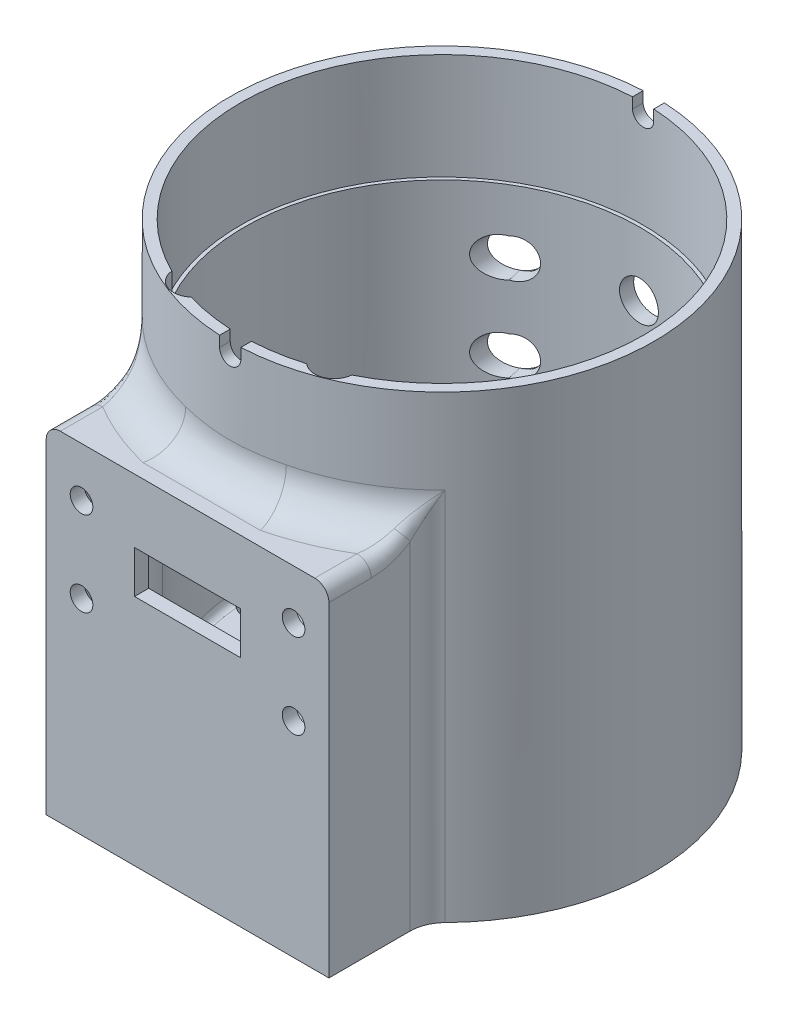
SolidWorks part; units mm, degrees
note: '?' marks a value the reader was unsure of.
material "自定义塑料"
ref_plane "前视基准面" through (0, 0, 0) normal (0, 0, 1) x (1, 0, 0)
ref_plane "上视基准面" through (0, 0, 0) normal (0, 1, 0) x (1, 0, 0)
ref_plane "右视基准面" through (0, 0, 0) normal (1, 0, 0) x (0, 0, -1)
sketch "草图1" plane through (0, 0, 0) normal (0, 1, 0) x (1, 0, 0)
  line L5 (15.5, 15.5) -> (-15.5, 15.5)
  line L6 (15.5, 15.5) -> (15.5, -15.5)
  line L7 (-3.3588, 3.3588) -> (3.3588, -3.3588) construction
  line L8 (15.5, -15.5) -> (-15.5, -15.5)
  line L9 (-15.5, 15.5) -> (-15.5, -15.5)
  line L10 (15.5, 15.5) -> (-15.5, -15.5) construction
  line L11 (15.5, -15.5) -> (-15.5, 15.5) construction
  circle A1 centre (0, 0) radius 30
  circle A6 centre (0, 0) radius 4.75
  circle A7 centre (-15.5, 15.5) radius 1.6
  circle A8 centre (15.5, 15.5) radius 1.6
  circle A9 centre (15.5, -15.5) radius 1.6
  circle A10 centre (-15.5, -15.5) radius 1.6
  point P17 (0, 0)
  point P20 (0, 0)
  dimension "D1" = 4
  dimension "D3" = 60
extrude "凸台-拉伸1" add sketch "草图1" along normal blind 5
sketch "草图2" plane through (0, 5, 0) normal (0, 1, 0) x (1, 0, 0)
  circle A0 centre (0, 0) radius 11.1
extrude "切除-拉伸1" cut sketch "草图2" against normal blind 2.2
sketch "草图4" plane through (0, 5, 0) normal (0, 1, 0) x (1, 0, 0)
  circle A0 centre (0, 0) radius 30
  circle A1 centre (0, 0) radius 28
extrude "凸台-拉伸2" add sketch "草图4" along normal blind 60
fillet "圆角1" radius 1 1 edges at (0, 5, 28)
ref_plane "基准面1" through (0, 0, 34) normal (0, 0, 1) x (1, 0, 0)
sketch "草图6" plane through (0, 0, 34) normal (0, 0, 1) x (1, 0, 0)
  line L0 (0, 0) -> (0, 7.1062)
  line L1 (-30, 0) -> (30, 0) construction
  line L2 (-18, 41) -> (-18, 5)
  line L3 (-15, 26) -> (15, 26)
  line L4 (-15, 26) -> (-15, 14)
  line L5 (-15, 14) -> (15, 14)
  line L6 (15, 26) -> (15, 14)
  line L7 (-15, 26) -> (15, 14) construction
  line L8 (-15, 14) -> (15, 26) construction
  line L13 (-10.8, 26) -> (10.8, 14) construction
  line L14 (-10.8, 14) -> (10.8, 26) construction
  line L19 (18, 41) -> (18, 5)
  line L20 (10, 26) -> (-16.6667, 10) construction
  line L23 (-20, 0) -> (20, 0)
  line L25 (-20, 0) -> (20, 0)
  line L27 (-18, 5) -> (18, 5)
  line L29 (-18, 5) -> (18, 5)
  line L31 (-20, 0) -> (20, 0)
  line L33 (-20, 42) -> (-20, 0)
  line L34 (0, 10) -> (0, 20)
  line L35 (10, 14) -> (-10, 26) construction
  line L36 (20, 42) -> (20, 0)
  line L37 (-20, 0) -> (-20, 48)
  line L38 (-20, 48) -> (20, 48)
  line L39 (20, 0) -> (20, 48)
  line L40 (-18, 0) -> (18, 0)
  line L41 (-18, 0) -> (-18, 46)
  line L42 (-18, 46) -> (18, 46)
  line L43 (18, 0) -> (18, 46)
  dimension "D6" = 42
  dimension "D1" = 20
  dimension "D2" = 41
  dimension "D3" = 36
  dimension "D4" = 30
  dimension "D5" = 12
  dimension "D7" = 42
  dimension "D8" = 5
  dimension "D9" = 40
extrude "凸台-拉伸3" add sketch "草图6" against normal blind 14.2
sketch "草图7" plane through (0, 65, 0) normal (0, 1, 0) x (1, 0, 0)
  circle A0 centre (0, 0) radius 28
extrude "切除-拉伸2" cut sketch "草图7" against normal blind 60
sketch "草图8" plane through (0, 0, 34) normal (0, 0, 1) x (1, 0, 0)
  line L33 (-18, 5) -> (-18, 46)
  line L34 (-18, 46) -> (18, 46)
  line L35 (18, 5) -> (18, 46)
  line L38 (18, 5) -> (-18, 5)
extrude "切除-拉伸3" cut sketch "草图8" against normal blind 26
fillet "圆角2" radius 5 3 edges at (20, 24, 22.3607) (-20, 24, 22.3607) (0, 48, 30)
fillet "圆角3" radius 10 3 edges at (-18, 25.5, 21.4476) (18, 25.5, 21.4476) (0, 46, 28)
sketch "草图9" plane through (0, 0, 34) normal (0, 0, 1) x (1, 0, 0)
  line L17 (-20, 0) -> (20, 0)
  line L18 (-20, 0) -> (-20, 48)
  line L19 (-20, 48) -> (20, 48)
  line L20 (20, 0) -> (20, 48)
extrude "凸台-拉伸4" add sketch "草图9" along normal blind 2
sketch "草图10" plane through (0, 0, 36) normal (0, 0, 1) x (1, 0, 0)
  line L12 (-15, 41) -> (15, 41)
  line L13 (-15, 41) -> (-15, 29)
  line L14 (-15, 29) -> (15, 29)
  line L15 (15, 41) -> (15, 29)
  line L16 (-15, 41) -> (15, 29) construction
  line L17 (-15, 29) -> (15, 41) construction
  circle A11 centre (-15, 41) radius 1.6
  circle A12 centre (15, 41) radius 1.6
  circle A13 centre (15, 29) radius 1.6
  circle A14 centre (-15, 29) radius 1.6
  point P0 (0, 35)
  dimension "D1" = 2
  dimension "D2" = 2
  dimension "D3" = 35
extrude "切除-拉伸4" cut sketch "草图10" against normal blind 2
ref_plane "基准面2" through (0, 0, -30) normal (0, 0, 1) x (1, 0, 0)
sketch "草图12" plane through (0, 0, -30) normal (0, 0, 1) x (1, 0, 0)
  line L2 (15, 29) -> (-15, 29)
  line L3 (15, 29) -> (15, 41)
  line L4 (15, 41) -> (-15, 41)
  line L5 (-15, 29) -> (-15, 41)
  line L6 (15, 29) -> (-15, 41) construction
  line L7 (15, 41) -> (-15, 29) construction
  circle A0 centre (-15, 29) radius 2.75
  circle A1 centre (-15, 41) radius 2.75
  circle A2 centre (15, 41) radius 2.75
  circle A3 centre (15, 29) radius 2.75
  point P0 (0, 35)
  dimension "D1" = 5.5
  dimension "D2" = 35
extrude "切除-拉伸5" cut sketch "草图12" along normal blind 13 contours A3 | A2 | A0 | A1
sketch "草图13" plane through (0, 0, -30) normal (0, 0, 1) x (1, 0, 0)
  line L0 (0, 14.25) -> (0, 19.75)
  line L2 (15, 29) -> (-15, 29)
  line L3 (15, 29) -> (15, 17)
  line L4 (15, 17) -> (-15, 17)
  line L5 (-15, 29) -> (-15, 17)
  line L6 (15, 29) -> (-15, 17) construction
  line L7 (15, 17) -> (-15, 29) construction
  circle A0 centre (0, 17) radius 2.75
  circle A3 centre (0, 29) radius 2.75
  circle A4 centre (0, 41) radius 2.75
  point P1 (0, 23)
  dimension "D1" = 23
ref_axis "基准轴1" through (0, 0, 0) along (0, 1, 0)?
extrude "切除-拉伸6" cut sketch "草图13" along normal blind 13
pattern_circular "阵列(圆周)1" count 2 every 30 about axis through (0, 0, 0) along (0, 1, 0) of "切除-拉伸6"
sketch "草图14" plane through (0, 65, 0) normal (0, 1, 0) x (1, 0, 0)
  circle A0 centre (0, 0) radius 28
  circle A1 centre (0, 0) radius 28.5
  dimension "D1" = 56
  dimension "D2" = 57
extrude "切除-拉伸7" cut sketch "草图14" against normal blind 15
sketch "草图15" plane through (0, 0, -30) normal (0, 0, 1) x (1, 0, 0)
  line L0 (30, 65) -> (-30, 65) construction
  line L7 (-1.5, 63.5) -> (-1.5, 66.5)
  line L8 (-1.5, 66.5) -> (1.5, 66.5)
  line L9 (1.5, 63.5) -> (1.5, 66.5)
  arc A1 (-1.5, 63.5) -> (1.5, 63.5) centre (0, 63.5) ccw
  point P0 (0, 65)
  point P8 (0, 65)
extrude "切除-拉伸8" cut sketch "草图15" along normal through all
sketch "草图16" plane through (0, 0, 0) normal (0, -1, 0) x (1, 0, 0)
  line L1 (15.5, -15.5) -> (-15.5, -15.5)
  line L2 (15.5, -15.5) -> (15.5, 15.5)
  line L3 (15.5, 15.5) -> (-15.5, 15.5)
  line L4 (-15.5, -15.5) -> (-15.5, 15.5)
  line L5 (15.5, -15.5) -> (-15.5, 15.5) construction
  line L6 (15.5, 15.5) -> (-15.5, -15.5) construction
  circle A0 centre (15.5, -15.5) radius 3
  circle A1 centre (-15.5, -15.5) radius 3
  circle A2 centre (-15.5, 15.5) radius 3
  circle A3 centre (15.5, 15.5) radius 3
  point P0 (0, 0)
  point P16 (0, 0)
  dimension "D1" = 4
extrude "切除-拉伸9" cut sketch "草图16" against normal blind 2 contours A0 | A1 | A3 | A2
fillet "圆角5" radius 2 6 edges at (20.3705, 50.9712, 22.6061) (20, 48.2483, 26.8048) (-20.3705, 50.9712, 22.6061) (-20, 48.4265, 26.2228) (20, 48, 32.3614) (-20, 48, 32.3614)
fillet "圆角6" radius 1 5 edges at (18, 5, 29.8452) (18.6811, 5, 22.0631) (-18, 5, 29.8452) (-18.6811, 5, 22.0631) (0, 5, -28)
sketch "草图17" plane through (0, 5, 0) normal (0, 1, 0) x (1, 0, 0)
  line L0 (0, 28) -> (0, 22.5)
  line L1 (0, 0) -> (0, -25.25)
  circle A0 centre (10, -25.25) radius 2.75
  arc A1 (20.6316, -18.9298) -> (-20.6316, -18.9298) centre (0, 0) ccw construction
  circle A2 centre (0, 25.25) radius 2.75
  circle A3 centre (25.25, 0) radius 2.75
  circle A4 centre (0, -25.25) radius 2.75
  circle A5 centre (-25.25, 0) radius 2.75
  circle A6 centre (-10, -25.25) radius 2.75
  point P18 (0, 0)
  dimension "D1" = 4
  dimension "D2" = 5.5
  dimension "D3" = 10
extrude "切除-拉伸10" cut sketch "草图17" against normal blind 2 and the other way through all contours A0 | A6 | A2 | A5 | A3
sketch "草图18" plane through (0, 3, 0) normal (0, 1, 0) x (1, 0, 0)
  circle A0 centre (0, 25.25) radius 1.5
  circle A1 centre (25.25, 0) radius 1.5
  circle A2 centre (0, -25.25) radius 1.5
  circle A3 centre (-25.25, 0) radius 1.5
  circle A4 centre (10, -25.25) radius 1.5
  circle A5 centre (-10, -25.25) radius 1.5
  point P12 (0, 0)
  dimension "D1" = 4
extrude "切除-拉伸11" cut sketch "草图18" against normal through all contours A4 | A1 | A0 | A3 | A5
sketch "草图19" plane through (0, 0, 36) normal (0, 0, 1) x (1, 0, 0)
  line L0 (0, 48) -> (0, 0)
  line L1 (-8.3066, 48) -> (8.3066, 48) construction
  line L2 (0, 0) -> (0, 24)
  line L3 (0, 24) -> (0, 48)
  line L5 (-7.5, 39) -> (7.5, 39)
  line L6 (-7.5, 39) -> (-7.5, 33)
  line L7 (-7.5, 33) -> (7.5, 33)
  line L8 (7.5, 39) -> (7.5, 33)
  line L9 (-7.5, 39) -> (7.5, 33) construction
  line L10 (-7.5, 33) -> (7.5, 39) construction
  point P6 (0, 36)
extrude "切除-拉伸12" cut sketch "草图19" against normal blind 2 contours L6 L7 L3 L5 | L8 L5 L3 L7
